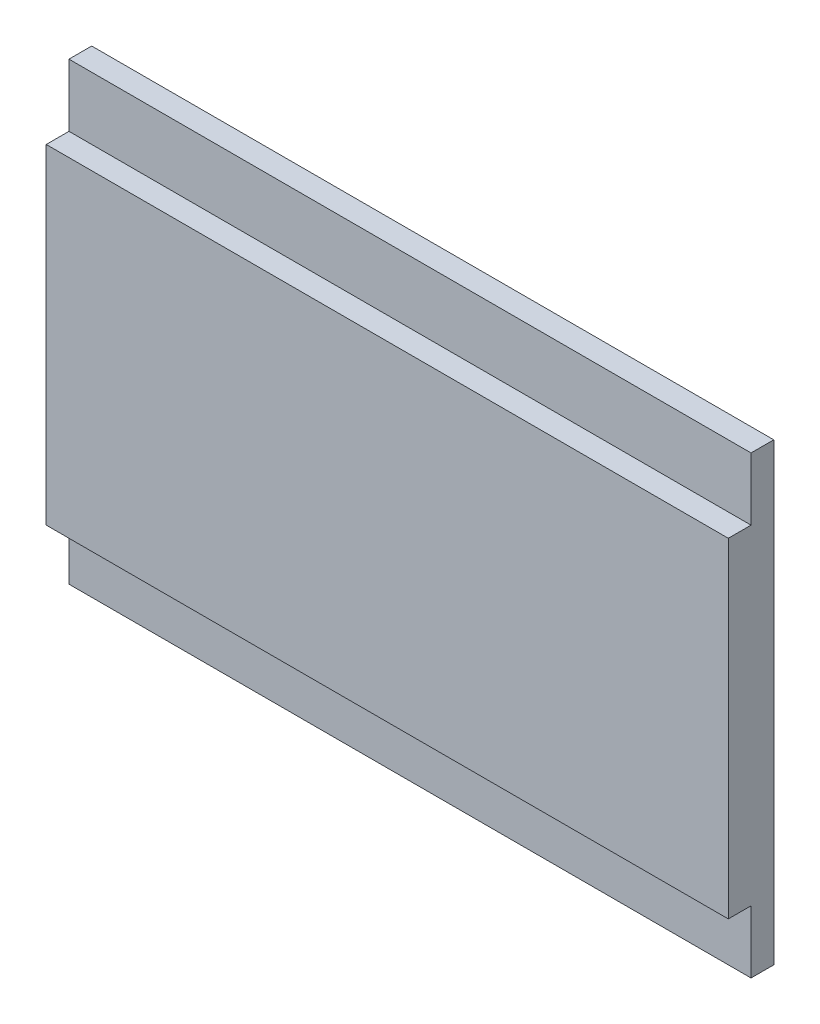
SolidWorks part; units mm, degrees
ref_plane "Front Plane" through (0, 0, 0) normal (0, 0, 1) x (1, 0, 0)
ref_plane "Top Plane" through (0, 0, 0) normal (0, 1, 0) x (1, 0, 0)
ref_plane "Right Plane" through (0, 0, 0) normal (1, 0, 0) x (0, 0, -1)
sketch "Sketch1" plane through (0, 0, 0) normal (0, 0, 1) x (1, 0, 0)
  line L0 (0, 100) -> (300, 100)
  line L1 (0, 0) -> (300, 0)
  line L2 (0, 0) -> (0, 200)
  line L3 (0, 200) -> (300, 200)
  line L4 (300, 0) -> (300, 200)
  line L6 (300, 172.5) -> (0, 172.5)
  line L7 (300, 172.5) -> (300, 27.5)
  line L8 (300, 27.5) -> (0, 27.5)
  line L9 (0, 172.5) -> (0, 27.5)
  line L10 (300, 172.5) -> (0, 27.5) construction
  line L11 (300, 27.5) -> (0, 172.5) construction
  point P7 (150, 100)
  dimension "D1" = 300
  dimension "D2" = 200
  dimension "D3" = 145
  dimension "D4" = 300
extrude "Boss-Extrude1" add sketch "Sketch1" along normal blind 10 contours L3 L4 L1 L2
extrude "Boss-Extrude2" add sketch "Sketch1<3>" along normal blind 20 contours L6 L9 L8 L7
sketch "Sketch1<3>" plane through (0, 0, 0) normal (0, 0, 1) x (1, 0, 0) same geometry as "Sketch1"
